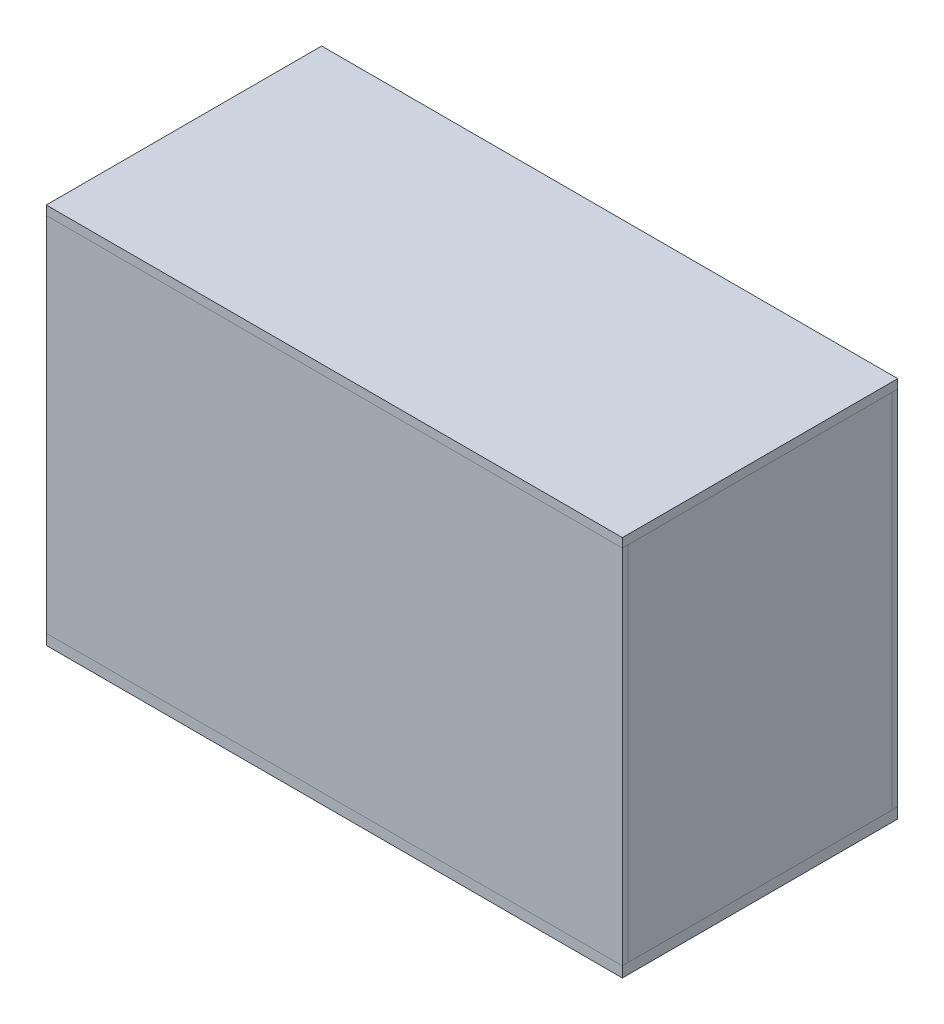
SolidWorks part; units mm, degrees
material "Acrylic (Medium-high impact)"
ref_plane "Front" through (0, 0, 0) normal (0, 0, 1) x (1, 0, 0)
ref_plane "Top" through (0, 0, 0) normal (0, 1, 0) x (1, 0, 0)
ref_plane "Right" through (0, 0, 0) normal (1, 0, 0) x (0, 0, -1)
sketch "Sketch1" plane through (0, 0, 0) normal (0, 1, 0) x (1, 0, 0)
  line L1 (-80.899, 38.6715) -> (80.899, 38.6715)
  line L2 (-80.899, 38.6715) -> (-80.899, -38.6715)
  line L3 (-80.899, -38.6715) -> (80.899, -38.6715)
  line L4 (80.899, 38.6715) -> (80.899, -38.6715)
  line L5 (-80.899, 38.6715) -> (80.899, -38.6715) construction
  line L6 (-80.899, -38.6715) -> (80.899, 38.6715) construction
  point P0 (0, 0)
  dimension "D1" = 77.343
  dimension "D2" = 161.798
extrude "Boss-Extrude1" add sketch "Sketch1" along normal blind 2.54
sketch "Sketch2" plane through (0, 2.54, 0) normal (0, 1, 0) x (1, 0, 0)
  line L0 (80.899, -38.6715) -> (80.899, 38.6715) construction
  line L1 (-71.374, 29.1465) -> (71.374, 29.1465) construction
  line L2 (-71.374, 29.1465) -> (-71.374, -29.1465) construction
  line L3 (-71.374, -29.1465) -> (71.374, -29.1465) construction
  line L4 (71.374, 29.1465) -> (71.374, -29.1465) construction
  line L5 (-71.374, 29.1465) -> (71.374, -29.1465) construction
  line L6 (-71.374, -29.1465) -> (71.374, 29.1465) construction
  line L7 (80.899, 38.6715) -> (-80.899, 38.6715) construction
  line L9 (-71.374, 29.1465) -> (-70.104, 29.1465)
  line L10 (-71.374, 29.1465) -> (-71.374, 27.8765)
  line L11 (-71.374, 27.8765) -> (-70.104, 27.8765)
  line L12 (-70.104, 29.1465) -> (-70.104, 27.8765)
  point P0 (0, 0)
  dimension "D1" = 9.525
  dimension "D2" = 9.525
  dimension "D3" = 1.27
  dimension "D4" = 1.27
extrude "Cut-Extrude1" [suppressed] cut sketch "Sketch2" against normal through all
pattern_linear "LPattern1" [suppressed] count 71 spacing 1.905 count 29 spacing 1.905 of bodies 180
sketch "Sketch3" [suppressed] plane through (0, 2.54, 0) normal (0, 1, 0) x (1, 0, 0)
  line L1 (-70.485, 29.1465) -> (64.135, 29.1465)
  line L2 (-70.485, 29.1465) -> (-70.485, -25.4635)
  line L3 (-70.485, -25.4635) -> (64.135, -25.4635)
  line L4 (64.135, 29.1465) -> (64.135, -25.4635)
extrude "Cut-Extrude2" [suppressed] cut sketch "Sketch3" against normal through all
sketch "WALL THICKNESS CONTROL" plane through (0, 0, 0) normal (0, -1, 0) x (1, 0, 0)
  line L0 (80.899, 38.6715) -> (80.899, -38.6715) construction
  line L1 (-80.899, 38.6715) -> (80.899, 38.6715)
  line L2 (-80.899, 38.6715) -> (-80.899, 37.084)
  line L3 (-80.899, 37.084) -> (80.899, 37.084)
  line L4 (80.899, 38.6715) -> (80.899, 37.084)
  line L5 (79.3115, 0) -> (80.899, 0) construction
  line L6 (-80.899, -38.6715) -> (80.899, -38.6715)
  line L7 (-80.899, -38.6715) -> (-80.899, -37.084)
  line L8 (-80.899, -37.084) -> (80.899, -37.084)
  line L9 (80.899, -38.6715) -> (80.899, -37.084)
  line L10 (80.899, 37.084) -> (79.3115, 37.084)
  line L11 (80.899, 37.084) -> (80.899, -37.084)
  line L12 (80.899, -37.084) -> (79.3115, -37.084)
  line L13 (79.3115, 37.084) -> (79.3115, -37.084)
  line L14 (-80.899, 37.084) -> (-79.3115, 37.084)
  line L15 (-80.899, 37.084) -> (-80.899, -37.084)
  line L16 (-80.899, -37.084) -> (-79.3115, -37.084)
  line L17 (-79.3115, 37.084) -> (-79.3115, -37.084)
  line L18 (-79.3115, 0) -> (-80.899, 0) construction
  dimension "D1" = 1.5875
sketch "Sketch5" plane through (0, 0, 0) normal (0, -1, 0) x (1, 0, 0)
  line L0 (-80.899, -37.084) -> (80.899, -37.084) construction
  line L1 (80.899, -38.6715) -> (80.899, -37.084) construction
  line L2 (-80.899, -38.6715) -> (80.899, -38.6715) construction
  line L3 (-80.899, -38.6715) -> (-80.899, -37.084) construction
  line L12 (-80.899, 37.084) -> (80.899, 37.084) construction
  line L13 (80.899, 38.6715) -> (80.899, 37.084) construction
  line L14 (-80.899, 38.6715) -> (80.899, 38.6715) construction
  line L15 (-80.899, 38.6715) -> (-80.899, 37.084) construction
  line L16 (-80.899, -37.084) -> (80.899, -37.084)
  line L17 (80.899, -38.6715) -> (80.899, -37.084)
  line L18 (-80.899, -38.6715) -> (80.899, -38.6715)
  line L19 (-80.899, -38.6715) -> (-80.899, -37.084)
  line L28 (-80.899, 37.084) -> (80.899, 37.084)
  line L29 (80.899, 38.6715) -> (80.899, 37.084)
  line L30 (-80.899, 38.6715) -> (80.899, 38.6715)
  line L31 (-80.899, 38.6715) -> (-80.899, 37.084)
extrude "Boss-Extrude2" add sketch "Sketch5" along normal blind 101.6 separate body
sketch "Sketch6" plane through (0, 0, 0) normal (0, -1, 0) x (1, 0, 0)
  line L4 (80.899, 37.084) -> (80.899, -37.084) construction
  line L5 (80.899, 37.084) -> (79.3115, 37.084) construction
  line L6 (79.3115, 37.084) -> (79.3115, -37.084) construction
  line L7 (80.899, -37.084) -> (79.3115, -37.084) construction
  line L8 (-80.899, 37.084) -> (-80.899, -37.084) construction
  line L9 (-80.899, 37.084) -> (-79.3115, 37.084) construction
  line L10 (-79.3115, 37.084) -> (-79.3115, -37.084) construction
  line L11 (-80.899, -37.084) -> (-79.3115, -37.084) construction
  line L20 (80.899, 37.084) -> (80.899, -37.084)
  line L21 (80.899, 37.084) -> (79.3115, 37.084)
  line L22 (79.3115, 37.084) -> (79.3115, -37.084)
  line L23 (80.899, -37.084) -> (79.3115, -37.084)
  line L24 (-80.899, 37.084) -> (-80.899, -37.084)
  line L25 (-80.899, 37.084) -> (-79.3115, 37.084)
  line L26 (-79.3115, 37.084) -> (-79.3115, -37.084)
  line L27 (-80.899, -37.084) -> (-79.3115, -37.084)
extrude "Boss-Extrude3" add sketch "Sketch6" along normal up to surface (101.6 mm away) separate body up to face at (0, -101.6, 37.8778)
sketch "Sketch7" plane through (0, -101.6, 0) normal (0, -1, 0) x (1, 0, 0)
  line L1 (-80.899, 38.6715) -> (80.899, 38.6715)
  line L2 (-80.899, 38.6715) -> (-80.899, -38.6715)
  line L3 (-80.899, -38.6715) -> (80.899, -38.6715)
  line L4 (80.899, 38.6715) -> (80.899, -38.6715)
extrude "Boss-Extrude4" add sketch "Sketch7" along normal blind 2.9718 separate body
sketch "Sketch14" plane through (0, 0, -38.6715) normal (0, 0, -1) x (-1, 0, 0)
  line L0 (80.899, -101.6) -> (-80.899, -101.6) construction
  line L1 (-78.6543, -50.8) -> (78.7234, -50.8)
  line L2 (-78.6543, -50.8) -> (-78.6543, -53.975)
  line L3 (-78.6543, -53.975) -> (78.7234, -53.975)
  line L4 (78.7234, -50.8) -> (78.7234, -53.975)
  line L5 (80.899, -101.6) -> (-80.899, -101.6) construction
  dimension "D1" = 47.625
  dimension "D2" = 50.8
sketch "Sketch9" plane through (0, 2.54, 0) normal (0, 1, 0) x (1, 0, 0)
  line L0 (-68.9615, 33.084) -> (-68.9615, 37.084) construction
  line L1 (-75.3115, 26.734) -> (-79.3115, 26.734) construction
  line L2 (80.899, 37.084) -> (-80.899, 37.084) construction
  line L3 (-79.3115, 37.084) -> (-79.3115, -37.084) construction
  circle A0 centre (-68.9615, 26.734) radius 6.35
  dimension "D1" = 12.7
  dimension "D2" = 4
  dimension "D3" = 4
extrude "Cut-Extrude4" [suppressed] cut sketch "Sketch9" against normal through all
sketch "Sketch13" plane through (0, 0, -38.6715) normal (0, 0, -1) x (-1, 0, 0)
  line L0 (0, 0) -> (0, -101.6) construction
  line L1 (80.899, 0) -> (-80.899, 0) construction
  line L2 (80.899, -101.6) -> (-80.899, -101.6) construction
  line L3 (-52.3875, -36) -> (52.3875, -36) construction
  circle A0 centre (-52.3875, -36) radius 3.175
  circle A1 centre (52.3875, -36) radius 3.175
  point P8 (0, -36)
  dimension "D2" = 6.35
  dimension "D1" = 104.775
  dimension "D3" = 36
extrude "Cut-Extrude7" [suppressed] cut sketch "Sketch13" against normal blind 2.9718
sketch "Sketch11" plane through (0, 0, -38.6715) normal (0, 0, 1) x (1, 0, 0)
  line L0 (0, 0) -> (0, -17.78) construction
  line L1 (0, -17.78) -> (-30, -17.78) construction
  line L2 (0, -17.78) -> (30, -17.78) construction
  line L5 (-80.899, 0) -> (80.899, 0) construction
  line L6 (80.899, -101.6) -> (80.899, 0) construction
  line L7 (0, 0) -> (0, -98.425) construction
  line L8 (-52.3875, -17.78) -> (52.3875, -17.78) construction
  line L9 (-80.899, 0) -> (80.899, 0) construction
  line L10 (-80.899, -101.6) -> (-80.899, 0) construction
  line L11 (-80.899, -104.5718) -> (80.899, -104.5718) construction
  circle A0 centre (-30, -17.78) radius 7.366
  circle A1 centre (30, -17.78) radius 7.366
  circle A2 centre (61.849, -47.625) radius 7.112
  circle A3 centre (-65.024, -44.2468) radius 7.112
  circle A4 centre (-52.3875, -17.78) radius 3.175
  circle A5 centre (52.3875, -17.78) radius 3.175
  point P19 (0, -17.78)
  dimension "D1" = 14.732
  dimension "D4" = 14.224
  dimension "D6" = 19.05
  dimension "D5" = 47.625
  dimension "D8" = 6.35
  dimension "D10" = 60.325
  dimension "D11" = 15.875
  dimension "D13" = 14.224
  dimension "D2" = 60
  dimension "D3" = 17.78
  dimension "D7" = 104.775
  dimension "D9" = 17.78
  dimension "D12" = 56.9468
extrude "Cut-Extrude5" cut sketch "Sketch11" along normal up to next (1.5875 mm away)
